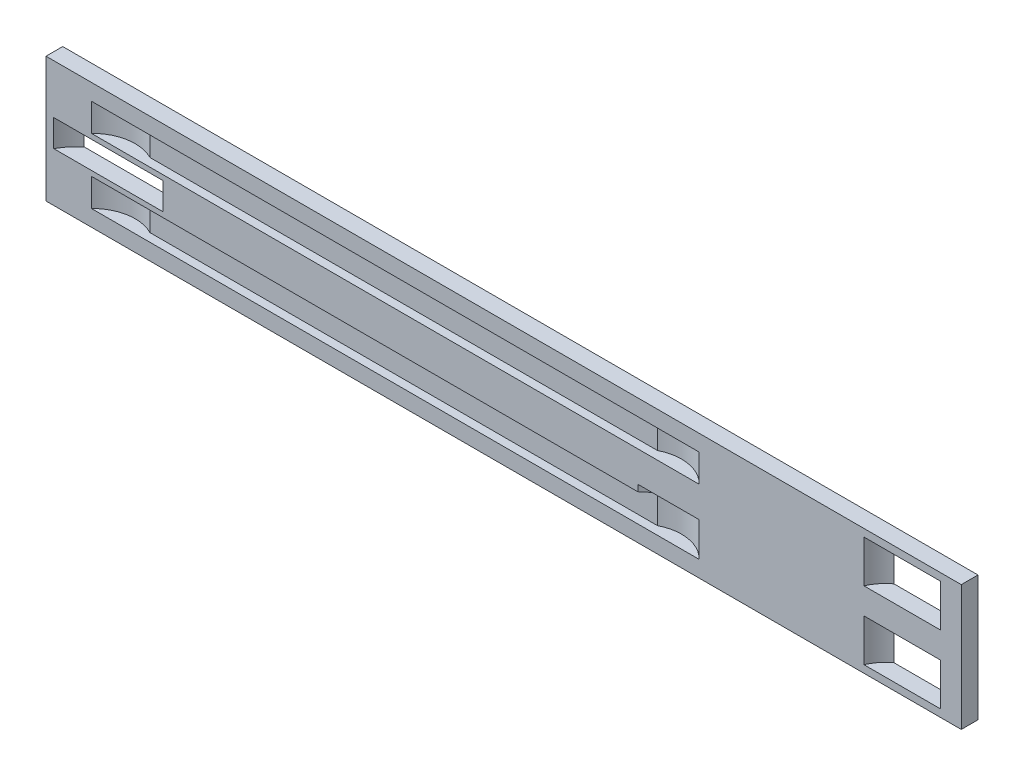
SolidWorks part; units mm, degrees
ref_plane "Alzado" through (0, 0, 0) normal (0, 0, 1) x (1, 0, 0)
ref_plane "Planta" through (0, 0, 0) normal (0, 1, 0) x (1, 0, 0)
ref_plane "Vista lateral" through (0, 0, 0) normal (1, 0, 0) x (0, 0, -1)
sketch "Croquis1" plane through (0, 0, 0) normal (0, 0, 1) x (1, 0, 0)
  line L0 (0, 0) -> (0, 135)
  line L1 (0, 135) -> (985, 135)
  line L2 (985, 135) -> (985, 0)
  line L3 (985, 0) -> (0, 0)
  dimension "D1" = 135
  dimension "D2" = 985
extrude "Saliente-Extruir1" add sketch "Croquis1" along normal blind 18
ref_plane "Plano1" through (0, 8, 0) normal (0, -1, 0) x (-1, 0, 0)
sketch "Croquis2" plane through (0, 8, 0) normal (0, -1, 0) x (-1, 0, 0)
  line L0 (-921.5, 0) -> (-921.5, -36) construction
  line L3 (0, 0) -> (-985, 0) construction
  circle A0 centre (-921.5, -36) radius 45
  dimension "D3" = 90
  dimension "D1" = 36
extrude "Cortar-Extruir1" cut sketch "Croquis2" against normal blind 45.5
ref_plane "Plano2" through (0, 67.5, 0) normal (0, 1, 0) x (1, 0, 0)
mirror "Simetría1" about plane through (0, 67.5, 0) normal (0, 1, 0) of "Cortar-Extruir1"
ref_plane "Plano3" through (0, 102.5, 0) normal (0, 1, 0) x (1, 0, 0)
sketch "Croquis5" plane through (0, 102.5, 0) normal (0, 1, 0) x (1, 0, 0)
  line L0 (82, 0) -> (82, -50) construction
  line L1 (0, 0) -> (985, 0) construction
  line L2 (0, -18) -> (0, 0) construction
  line L3 (102.8567, 0) -> (102.8567, -9) construction
  line L5 (102.8567, -9) -> (649.0525, -9)
  line L6 (48.9546, -18) -> (702.9546, -18)
  line L7 (0, -18) -> (985, -18) construction
  line L8 (375.9546, -18) -> (375.9546, 101.3461) construction
  arc A0 (102.8567, -9) -> (48.9546, -18) centre (82, -50) ccw
  arc A1 (649.0525, -9) -> (702.9546, -18) centre (669.9092, -50) cw
  dimension "D2" = 82
  dimension "D1" = 50
  dimension "D3" = 654
extrude "Cortar-Extruir3" cut sketch "Croquis5" against normal mid plane 30
mirror "Simetría5" about plane through (0, 67.5, 0) normal (0, 1, 0) of "Cortar-Extruir3"
sketch "Croquis7" plane through (0, 47.5, 0) normal (0, -1, 0) x (1, 0, 0)
  circle A0 centre (669.9092, 50) radius 46
  arc A1 (649.0525, 9) -> (702.9546, 18) centre (669.9092, 50) ccw construction
extrude "Cortar-Extruir4" cut sketch "Croquis7" against normal blind 7
sketch "Croquis10" plane through (0, 67.5, 0) normal (0, 1, 0) x (1, 0, 0)
  line L0 (0, -9) -> (67, -9) construction
  line L1 (0, -18) -> (0, 0) construction
  line L2 (67, -9) -> (67, -51.2) construction
  circle A0 centre (67, -51.2) radius 67.5
  dimension "D3" = 135
  dimension "D1" = 67
  dimension "D2" = 42.2
extrude "Cortar-Extruir5" cut sketch "Croquis10" against normal mid plane 29
